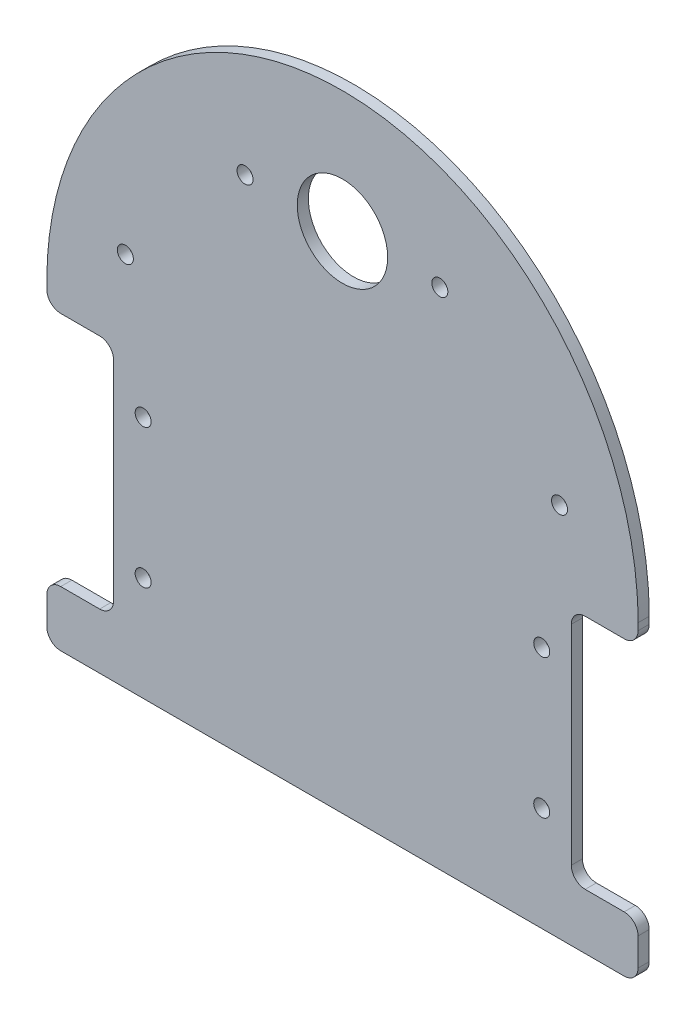
SolidWorks part; units mm, degrees
material "A-Glass Fiber"
ref_plane "Top Plane" through (0, 0, 0) normal (0, 0, 1) x (1, 0, 0)
ref_plane "Right Plane" through (0, 0, 0) normal (0, 1, 0) x (1, 0, 0)
ref_plane "Front Plane" through (0, 0, 0) normal (1, 0, 0) x (0, 0, -1)
sketch "Sketch1" plane through (0, 0, 0) normal (0, 0, 1) x (1, 0, 0)
  line L1 (42.5, -45) -> (-42.5, -45)
  line L2 (42.5, -45) -> (42.5, 45)
  line L3 (42.5, 45) -> (-42.5, 45)
  line L4 (-42.5, -45) -> (-42.5, 45)
  line L5 (42.5, -45) -> (-42.5, 45) construction
  line L6 (42.5, 45) -> (-42.5, -45) construction
  point P0 (0, 0)
  dimension "D1" = 85
  dimension "D2" = 90
extrude "Boss-Extrude1" add sketch "Sketch1" along normal blind 1.6
sketch "Sketch2" plane through (0, 0, 1.6) normal (0, 0, 1) x (1, 0, 0)
  line L0 (-42.5, 45) -> (-42.5, -45) construction
  line L1 (42.5, 45) -> (-42.5, 45) construction
  line L6 (-42.5, 0) -> (-70, 0)
  line L7 (-70, 0) -> (-70, 70)
  line L8 (42.5, -45) -> (42.5, 45) construction
  line L9 (-70, 70) -> (70, 70)
  line L10 (70, 70) -> (70, 0)
  line L11 (70, 0) -> (42.5, 0)
  ellipse E0 centre (0, 0) end of major axis (0, -45) minor radius 42.5 (42.5, 0) -> (-42.5, 0) ccw
  point P14 (0, 70)
  dimension "D1" = 140
  dimension "D2" = 70
extrude "Cut-Extrude1" cut sketch "Sketch2" against normal through all
sketch "Sketch3" plane through (0, 0, 1.6) normal (0, 0, 1) x (1, 0, 0)
  line L1 (-42.5, -3) -> (-32.9, -3)
  line L2 (-42.5, -3) -> (-42.5, -37)
  line L3 (-42.5, -37) -> (-32.9, -37)
  line L4 (-32.9, -3) -> (-32.9, -37)
  line L6 (0, -0.88) -> (0, 0.88) construction
  line L7 (42.5, -3) -> (32.9, -3)
  line L8 (42.5, -37) -> (32.9, -37)
  line L9 (32.9, -3) -> (32.9, -37)
  line L10 (42.5, -3) -> (42.5, -37)
  line L11 (-42.5, 0) -> (-42.5, -45) construction
  line L13 (-42.5, -45) -> (42.5, -45) construction
  dimension "D1" = 9.6
  dimension "D2" = 34
  dimension "D3" = 8
extrude "Cut-Extrude2" cut sketch "Sketch3" against normal through all
sketch "Sketch4" plane through (0, 0, 1.6) normal (0, 0, 1) x (1, 0, 0)
  line L0 (-42.5, -45) -> (42.5, -45) construction
  circle A0 centre (0, 27.5) radius 6.5
  dimension "D1" = 13
  dimension "D2" = 72.5
extrude "Cut-Extrude3" cut sketch "Sketch4" against normal through all
sketch "Sketch5" plane through (0, 0, 1.6) normal (0, 0, 1) x (1, 0, 0)
  line L1 (-32.9, -37) -> (-32.9, -3) construction
  line L2 (-28.65, -10) -> (-28.65, -30) construction
  line L3 (0, -0.88) -> (0, 0.88) construction
  line L4 (-1016.15, -20) -> (48983.85, -20) construction
  line L5 (0, -1000) -> (0, 49000) construction
  circle A0 centre (-28.65, -10) radius 1.15
  circle A1 centre (-28.65, -30) radius 1.15
  circle A2 centre (28.65, -30) radius 1.15
  circle A3 centre (28.65, -10) radius 1.15
  point P2 (-28.65, -20)
  point P14 (-32.9, -20)
  dimension "D3" = 2.3
  dimension "D1" = 4.25
  dimension "D2" = 20
extrude "Cut-Extrude4" cut sketch "Sketch5" against normal through all
sketch "Sketch6" plane through (0, 0, 1.6) normal (0, 0, 1) x (1, 0, 0)
  line L0 (-14, 27.5) -> (14, 27.5) construction
  circle A1 centre (-14, 27.5) radius 1.15
  circle A2 centre (14, 27.5) radius 1.15
  point P5 (0, 27.5)
  dimension "D2" = 2.3
  dimension "D1" = 28
extrude "Cut-Extrude5" cut sketch "Sketch6" against normal through all
fillet "Fillet1" radius 2 10 edges at (42.5, -37, 0.8) (32.9, -37, 0.8) (32.9, -3, 0.8) (42.5, -3, 0.8) (-32.9, -37, 0.8) (-32.9, -3, 0.8) (-42.5, -37, 0.8) (-42.5, -3, 0.8) (42.5, -45, 0.8) (-42.5, -45, 0.8)
sketch "Sketch7" plane through (0, 0, 1.6) normal (0, 0, 1) x (1, 0, 0)
  line L0 (-40.5, -45) -> (40.5, -45) construction
  line L1 (0, -63.3642) -> (0, 76.6358) construction
  line L2 (-31.2085, 9) -> (31.2085, 9) construction
  circle A0 centre (-31.2085, 9) radius 1.15
  circle A1 centre (31.2085, 9) radius 1.15
  point P4 (0, 9)
  dimension "D1" = 2.3
  dimension "D2" = 54
  dimension "D3" = 62.417
extrude "Cut-Extrude6" cut sketch "Sketch7" against normal blind 10
equation "\"Motor_Position\"= 8"
equation "\"D3@Sketch3\"=\"Motor_Position\""
equation "\"Caster_Position\"= 72.5"
equation "\"D2@Sketch4\"=\"Caster_Position\""
equation "\"Battery_position\" = 54mm"
equation "\"D2@Sketch7\"=\"Battery_position\""
